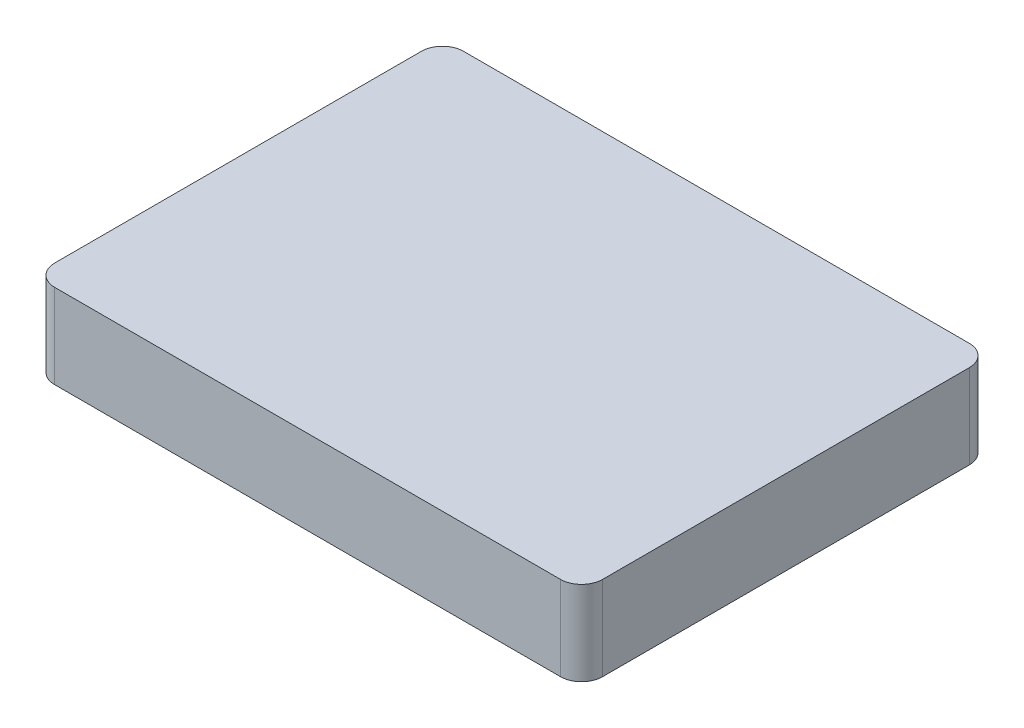
SolidWorks part; units mm, degrees
material "Plain Carbon Steel"
ref_plane "Front Plane" through (0, 0, 0) normal (0, 0, 1) x (1, 0, 0)
ref_plane "Top Plane" through (0, 0, 0) normal (0, 1, 0) x (1, 0, 0)
ref_plane "Right Plane" through (0, 0, 0) normal (1, 0, 0) x (0, 0, -1)
sketch "Sketch1" plane through (0, 0, 0) normal (0, 1, 0) x (1, 0, 0)
  line L1 (-65, -48.5) -> (65, -48.5)
  line L2 (-65, -48.5) -> (-65, 48.5)
  line L3 (-65, 48.5) -> (65, 48.5)
  line L4 (65, -48.5) -> (65, 48.5)
  line L5 (-65, -48.5) -> (65, 48.5) construction
  line L6 (-65, 48.5) -> (65, -48.5) construction
  point P0 (0, 0)
  dimension "D1" = 130
  dimension "D2" = 97
extrude "Boss-Extrude1" add sketch "Sketch1" against normal blind 20
fillet "Fillet1" radius 5 4 edges at (-65, -10, -48.5) (-65, -10, 48.5) (65, -10, -48.5) (65, -10, 48.5)
